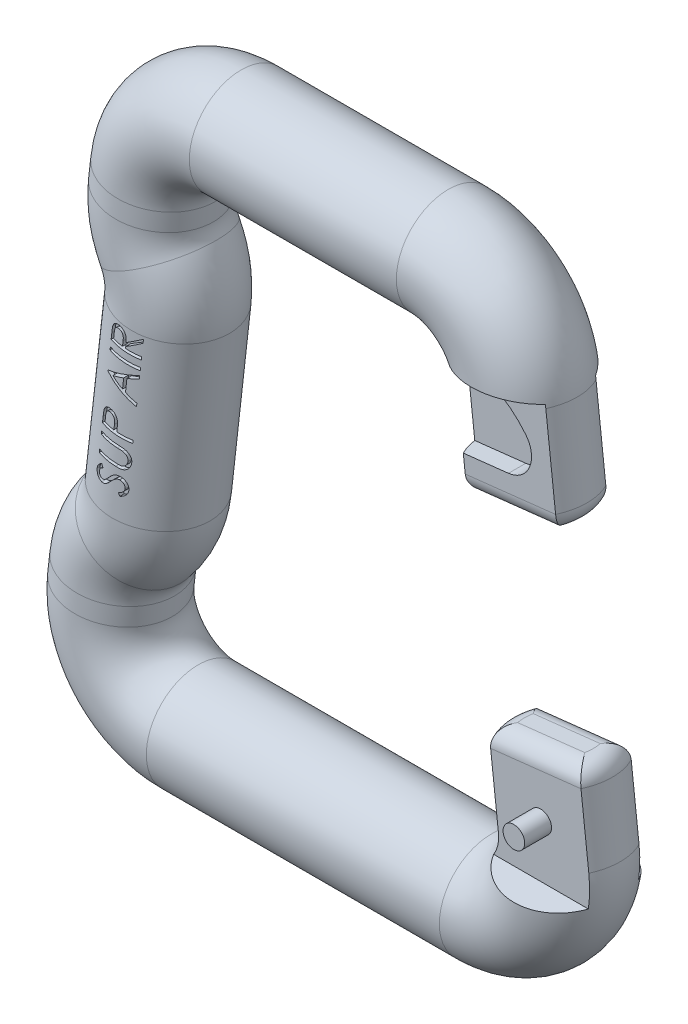
SolidWorks part; units mm, degrees
material "1.0037 (S235JR)"
ref_plane "Front Plane" through (0, 0, 0) normal (0, 0, 1) x (1, 0, 0)
ref_plane "Top Plane" through (0, 0, 0) normal (0, 1, 0) x (1, 0, 0)
ref_plane "Right Plane" through (0, 0, 0) normal (1, 0, 0) x (0, 0, -1)
sketch "Sketch1" plane through (0, 0, 0) normal (0, 0, 1) x (1, 0, 0)
  line L0 (0, 31) -> (0, -31) construction
  line L1 (-16.9267, -31) -> (16.9267, -31)
  line L2 (-25.8699, -20.9903) -> (-25.6231, -18.8042)
  line L3 (-11.9589, 31) -> (11.9589, 31)
  line L4 (25.8699, -20.9903) -> (24.7419, -11)
  line L5 (-19.2819, 10.62) -> (-21.5257, -9.2537)
  line L6 (-19.2819, 10.62) -> (-33.2926, 12.2019) construction
  line L7 (-21.5257, -9.2537) -> (-33.3624, -7.9173) construction
  line L9 (-21.1467, 20.8437) -> (-20.9021, 23.0097)
  line L10 (5.5764, -11) -> (36.6748, -11) construction
  line L11 (8.7036, 11) -> (34.0688, 11) construction
  line L12 (22.2581, 11) -> (20.9021, 23.0097)
  arc A0 (-21.1467, 20.8437) -> (-20.2143, 15.7319) centre (-12.2035, 19.834) ccw
  arc A1 (-19.2819, 10.62) -> (-20.2143, 15.7319) centre (-28.2251, 11.6298) ccw
  arc A2 (-23.5744, -14.0289) -> (-21.5257, -9.2537) centre (-30.4689, -8.244) ccw
  arc A3 (-23.5744, -14.0289) -> (-25.6231, -18.8042) centre (-16.6799, -19.8139) ccw
  arc A4 (16.9267, -31) -> (25.8699, -20.9903) centre (16.9267, -22) ccw
  arc A5 (-16.9267, -31) -> (-25.8699, -20.9903) centre (-16.9267, -22) cw
  arc A6 (11.9589, 31) -> (20.9021, 23.0097) centre (11.9589, 22) cw
  arc A7 (-20.9021, 23.0097) -> (-11.9589, 31) centre (-11.9589, 22) cw
  point P0 (0, 0)
  point P24 (27, -31)
  point P27 (-27, -31)
  point P30 (20, 31)
  point P33 (-20, 31)
  dimension "D6" = 9
  dimension "D7" = 9
  dimension "D8" = 9
  dimension "D9" = 9
  dimension "D10" = 9
  dimension "D1" = 62
  dimension "D2" = 54
  dimension "D3" = 40
  dimension "D4" = 3
  dimension "D5" = 20
  dimension "D11" = 20
  dimension "D12" = 20
  dimension "D13" = 2.2
ref_plane "Plane1" through (24.7419, -11, 0) normal (-0.1122, 0.9937, 0) x (0.9937, 0.1122, 0)
sketch "Sketch2" plane through (24.7419, -11, 0) normal (-0.1122, 0.9937, 0) x (0.9937, 0.1122, 0)
  circle A0 centre (0, 0) radius 6
  dimension "D1" = 12
sweep "Sweep1" add profiles "Sketch2" path "Sketch1"
sketch "Sketch3" plane through (0, 0, 0) normal (1, 0, 0) x (0, 0, -1)
  line L0 (-6, 24.5466) -> (-2.9, 24)
  line L1 (-6, 23.0097) -> (-6, 11) construction
  line L2 (-2.9, 24) -> (-2.9, -24)
  line L3 (-2.9, -24) -> (-6, -24.5466)
  line L4 (-6, -20.9903) -> (-6, -31) construction
  line L5 (-6, -24.5466) -> (-6, 24.5466)
  dimension "D1" = 2.9
  dimension "D2" = 80
  dimension "D3" = 80
  dimension "D4" = 24
  dimension "D5" = 24
extrude "Cut-Extrude1" cut sketch "Sketch3" along normal through all
mirror "Mirror1" about plane through (0, 0, 0) normal (0, 0, 1) of "Cut-Extrude1"
sketch "Sketch4" plane through (0, 0, 0) normal (0, 0, 1) x (1, 0, 0)
  line L0 (18.7798, -11.6731) -> (19.9078, -21.6634) construction
  line L1 (16.9267, -25) -> (-16.9267, -25) construction
  circle A0 centre (25.5323, -18) radius 1.25
  dimension "D1" = 2.5
  dimension "D2" = 6
  dimension "D3" = 7
sketch "Sketch5" plane through (0, 0, 2.9) normal (0, 0, 1) x (1, 0, 0)
  line L0 (15.128, 24) -> (13.0783, 24)
  line L1 (13.0783, 24) -> (13.0783, 13.989)
  line L2 (13.0783, 13.989) -> (21.8093, 14.9747)
  line L3 (17.0386, 10.4107) -> (27.4775, 11.5893) construction
  line L4 (14.94, 22.3366) -> (16.2959, 10.3269) construction
  arc A0 (15.128, 24) -> (23.8128, 19.833) centre (15.128, 12.866) cw
  arc A1 (23.8128, 19.833) -> (21.8093, 14.9747) centre (21.4727, 17.9558) cw
  dimension "D2" = 3
  dimension "D1" = 4
  dimension "D3" = 6
extrude "Cut-Extrude3" cut sketch "Sketch5" against normal blind 2
mirror "Mirror2" about plane through (0, 0, 0) normal (0, 0, 1) of "Cut-Extrude3"
fillet "Fillet1" radius 2 4 edges at (22.2581, 11, 2.9) (28.2202, 11.6731, 0) (22.2581, 11, -2.9) (16.2959, 10.3269, 0)
fillet "Fillet2" radius 2 4 edges at (30.7041, -10.3269, 0) (24.7419, -11, 2.9) (18.7798, -11.6731, 0) (24.7419, -11, -2.9)
ref_plane "Plane2" through (0, 0, 5.4) normal (0, 0, 1) x (1, 0, 0)
sketch "Sketch6" plane through (0, 0, 5.4) normal (0, 0, 1) x (1, 0, 0)
  line L0 (-19.2819, 10.62) -> (-21.5257, -9.2537) construction
  line L1 (-13.3198, 9.9469) -> (-25.244, 11.2932) construction
  line L2 (-15.5636, -9.9268) -> (-27.4878, -8.5805) construction
  line L3 (-17.4933, 10.4181) -> (-19.7371, -9.4556) construction
  text T0 "SUP AIR"
  dimension "D1" = 1.8
extrude "Cut-Extrude4" cut sketch "Sketch6" along normal blind 2
extrude "Boss-Extrude1" add sketch "Sketch4" along normal mid plane 12
